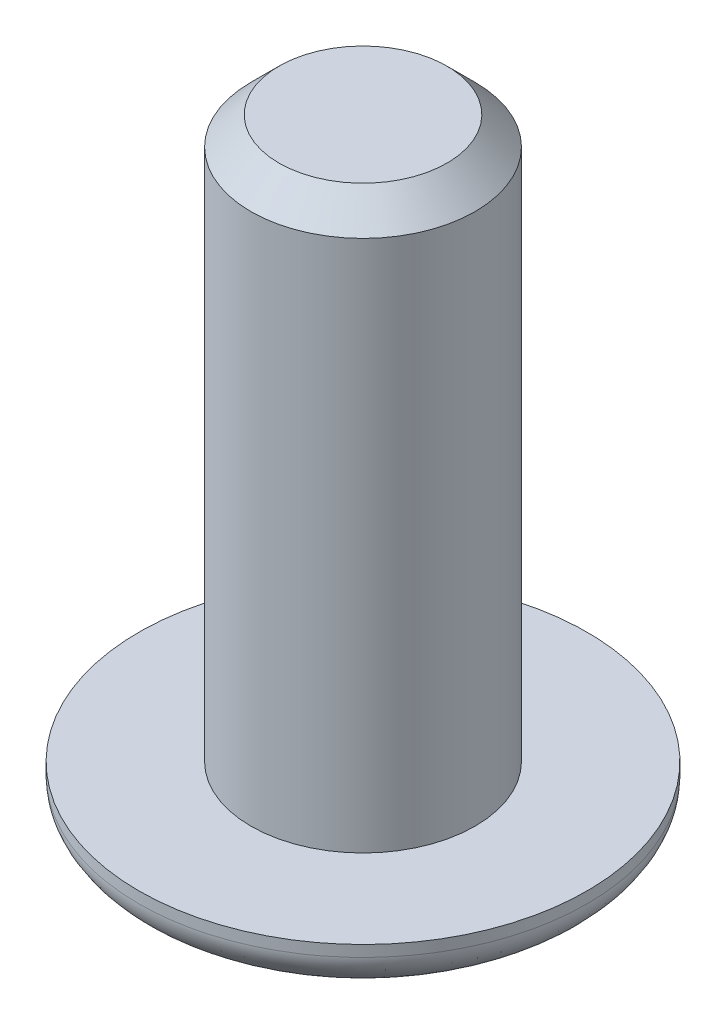
SolidWorks part; units mm, degrees
material "ASTM A36 钢"
ref_plane "前视基准面" through (0, 0, 0) normal (0, 0, 1) x (1, 0, 0)
ref_plane "上视基准面" through (0, 0, 0) normal (0, 1, 0) x (1, 0, 0)
ref_plane "右视基准面" through (0, 0, 0) normal (1, 0, 0) x (0, 0, -1)
sketch "草图1" plane through (0, 0, 0) normal (0, 1, 0) x (1, 0, 0)
  line L1 (1.4434, 0) -> (0.7217, 1.25)
  line L2 (0.7217, 1.25) -> (-0.7217, 1.25)
  line L3 (-0.7217, 1.25) -> (-1.4434, 0)
  line L4 (-1.4434, 0) -> (-0.7217, -1.25)
  line L5 (-0.7217, -1.25) -> (0.7217, -1.25)
  line L6 (0.7217, -1.25) -> (1.4434, 0)
  circle A0 centre (0, 0) radius 4
  circle A1 centre (0, 0) radius 1.25 construction
extrude "凸台-拉伸1" add sketch "草图1" along normal blind 1.2
sketch "草图2" plane through (0, 1.2, 0) normal (0, 1, 0) x (1, 0, 0)
  circle A0 centre (0, 0) radius 2
extrude "凸台-拉伸2" add sketch "草图2" along normal blind 10
chamfer "倒角1" distance 0.5 angle 45 1 edges at (0, 11.2, 2)
fillet "圆角1" radius 2 1 edges at (0, 0, 4) second distance 1 first distance on face at (0, 0, 4)
